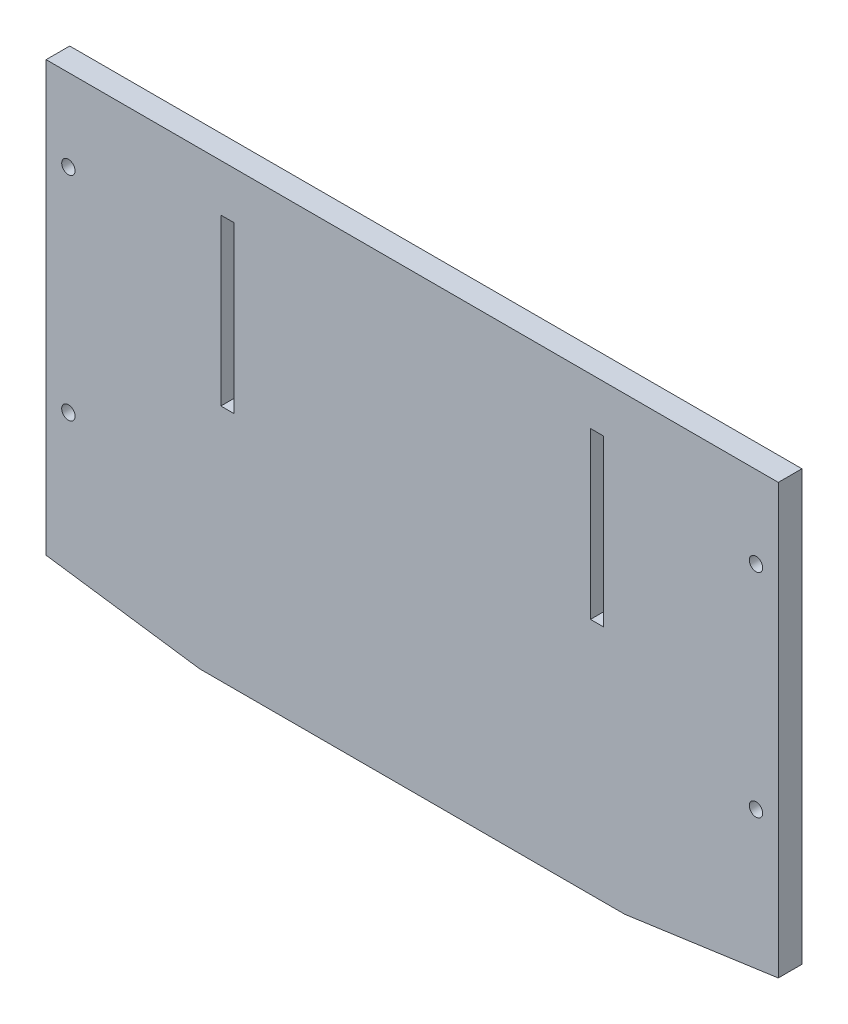
SolidWorks part; units mm, degrees
material "Acrylic (Medium-high impact)"
ref_plane "Front Plane" through (0, 0, 0) normal (0, 0, 1) x (1, 0, 0)
ref_plane "Top Plane" through (0, 0, 0) normal (0, 1, 0) x (1, 0, 0)
ref_plane "Right Plane" through (0, 0, 0) normal (1, 0, 0) x (0, 0, -1)
sketch "Sketch1" plane through (0, 0, 0) normal (0, 0, 1) x (1, 0, 0)
  line L1 (196.85, 127) -> (0, 127)
  line L2 (196.85, 127) -> (196.85, 0)
  line L3 (196.85, 0) -> (0, 0)
  line L4 (0, 127) -> (0, 0)
  line L5 (196.85, 127) -> (0, 0) construction
  line L6 (196.85, 0) -> (0, 127) construction
  point P0 (98.425, 63.5)
  dimension "D1" = 127
  dimension "D2" = 196.85
extrude "Boss-Extrude1" add sketch "Sketch1" along normal blind 6.35
hole_wizard "M3 Clearance Hole1" positions "Sketch2" profile "Sketch3" hole size "M3" standard "ANSI Metric" end condition through all
sketch "Sketch2" plane through (0, 0, 6.35) normal (0, 0, 1) x (1, 0, 0)
  line L0 (0, 127) -> (0, 0) construction
  line L1 (196.85, 127) -> (0, 127) construction
  line L2 (196.85, 0) -> (196.85, 127) construction
  point P0 (5.9944, 105.0036)
  point P2 (5.9944, 47.8536)
  point P4 (190.8556, 47.8536)
  point P6 (190.8556, 105.0036)
  dimension "D1" = 5.9944
  dimension "D2" = 21.9964
  dimension "D3" = 5.9944
  dimension "D4" = 57.15
sketch "Sketch3" plane through (5.9944, 105.0036, 6.35) normal (1, 0, 0) x (0, -1, 0)
  line L0 (0, 0) -> (0, 6.35)
  line L1 (0, 6.35) -> (1.8, 6.35)
  line L2 (1.8, 6.35) -> (1.8, 0)
  line L5 (1.8, 0) -> (0, 0)
  line L11 (0, -6.35) -> (0, 107.95) construction
  dimension "Thru Hole Dia." = 3.6
  dimension "Thru Hole Depth" = 6.35
sketch "Sketch4" plane through (0, 0, 6.35) normal (0, 0, 1) x (1, 0, 0)
  line L0 (0, 127) -> (0, 0) construction
  line L1 (46.99, 114.3) -> (50.4952, 114.3)
  line L2 (46.99, 114.3) -> (46.99, 69.85)
  line L3 (46.99, 69.85) -> (50.4952, 69.85)
  line L4 (50.4952, 114.3) -> (50.4952, 69.85)
  line L5 (146.3548, 114.3) -> (149.86, 114.3)
  line L6 (146.3548, 114.3) -> (146.3548, 69.85)
  line L7 (146.3548, 69.85) -> (149.86, 69.85)
  line L8 (149.86, 114.3) -> (149.86, 69.85)
  line L9 (196.85, 0) -> (196.85, 127) construction
  line L10 (196.85, 127) -> (0, 127) construction
  dimension "D1" = 3.5052
  dimension "D2" = 44.45
  dimension "D3" = 46.99
  dimension "D4" = 46.99
  dimension "D5" = 12.7
extrude "Cut-Extrude1" cut sketch "Sketch4" against normal through all
sketch "Sketch5" plane through (0, 0, 6.35) normal (0, 0, 1) x (1, 0, 0)
  line L0 (0, 11.6016) -> (82.55, 0)
  line L1 (0, 127) -> (0, 0) construction
  line L2 (0, 0) -> (196.85, 0) construction
  line L3 (82.55, 0) -> (0, 0)
  line L4 (0, 0) -> (0, 11.6016)
  line L5 (114.3, 0) -> (196.85, 0)
  line L6 (196.85, 0) -> (196.85, 11.6016)
  line L7 (196.85, 0) -> (196.85, 127) construction
  line L8 (196.85, 11.6016) -> (114.3, 0)
  dimension "D1" = 8
  dimension "D2" = 8
  dimension "D3" = 31.75
extrude "Cut-Extrude2" cut sketch "Sketch5" against normal through all
sketch "Sketch6" plane through (0, 0, 6.35) normal (0, 0, 1) x (1, 0, 0)
  line L1 (41.275, -0.5492) -> (155.575, -0.5492)
  line L2 (41.275, -0.5492) -> (41.275, 5.8008)
  line L3 (41.275, 5.8008) -> (155.575, 5.8008)
  line L4 (155.575, -0.5492) -> (155.575, 5.8008)
  line L5 (196.85, 11.6016) -> (114.3, 0) construction
  line L6 (82.55, 0) -> (0, 11.6016) construction
  dimension "D1" = 6.35
extrude "Cut-Extrude3" cut sketch "Sketch6" against normal through all
